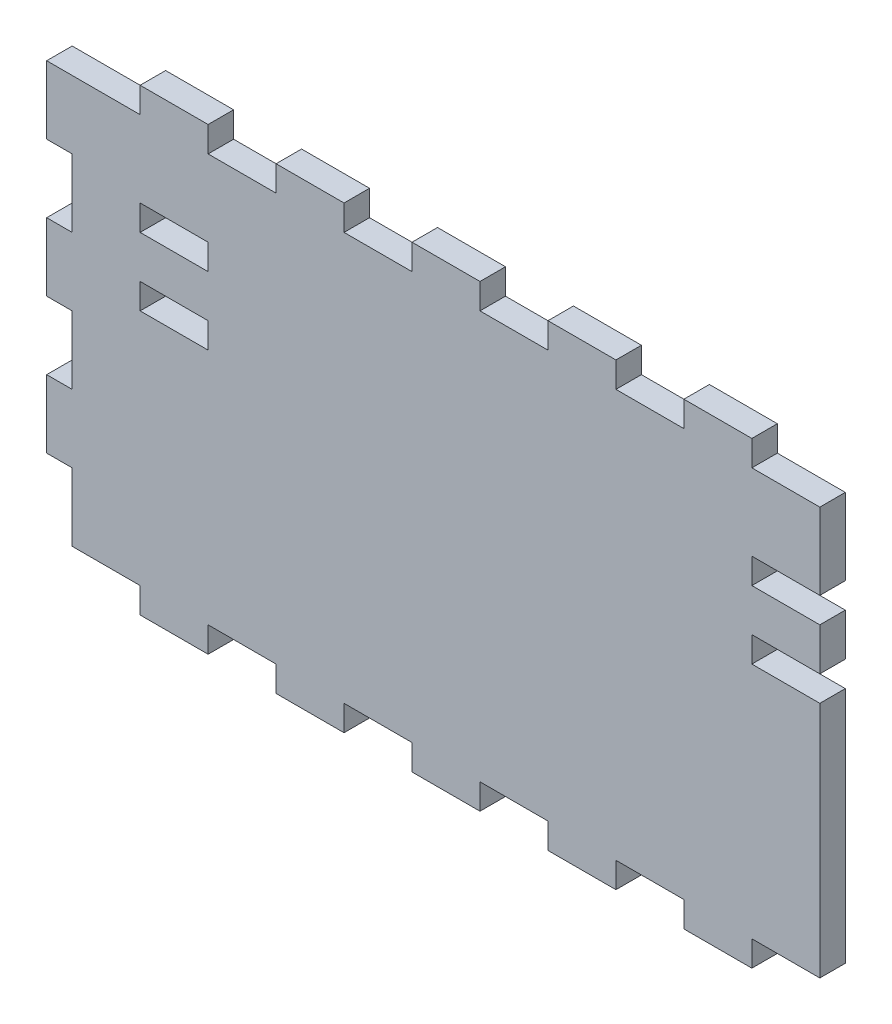
SolidWorks part; units mm, degrees
ref_plane "Front Plane" through (0, 0, 0) normal (0, 0, 1) x (1, 0, 0)
ref_plane "Top Plane" through (0, 0, 0) normal (0, 1, 0) x (1, 0, 0)
ref_plane "Right Plane" through (0, 0, 0) normal (1, 0, 0) x (0, 0, -1)
sketch "Sketch1" plane through (0, 0, 0) normal (0, 0, 1) x (1, 0, 0)
  line L1 (-139.7, -76.2) -> (139.7, -76.2)
  line L2 (-139.7, -76.2) -> (-139.7, 76.2)
  line L3 (-139.7, 76.2) -> (139.7, 76.2)
  line L4 (139.7, -76.2) -> (139.7, 76.2)
  line L5 (-139.7, -76.2) -> (139.7, 76.2) construction
  line L6 (-139.7, 76.2) -> (139.7, -76.2) construction
  point P0 (0, 0)
  dimension "D1" = 279.4
  dimension "D2" = 152.4
extrude "Boss-Extrude1" add sketch "Sketch1" along normal blind 9.525
sketch "Sketch2" plane through (0, -76.2, 0) normal (0, -1, 0) x (1, 0, 0)
  line L0 (-139.7, 0) -> (139.7, 0) construction
  line L1 (-114.3, 0) -> (-88.9, 0)
  line L2 (-114.3, 0) -> (-114.3, 9.525)
  line L3 (-114.3, 9.525) -> (-88.9, 9.525)
  line L4 (-88.9, 0) -> (-88.9, 9.525)
  line L5 (-139.7, 9.525) -> (139.7, 9.525) construction
  line L6 (-139.7, 9.525) -> (-139.7, 0) construction
  point P10 (-139.7, 4.7625)
  dimension "D1" = 25.4
  dimension "D2" = 25.4
extrude "Boss-Extrude2" add sketch "Sketch2" along normal blind 9.525
pattern_linear "LPattern1" count 5 spacing 50.8 along (1, 0, 0) of "Boss-Extrude2"
mirror "Mirror1" about plane through (0, 0, 0) normal (0, 1, 0) of "LPattern1"
sketch "Sketch3" plane through (-139.7, 0, 0) normal (-1, 0, 0) x (0, 0, 1)
  line L0 (0, 76.2) -> (0, -76.2) construction
  line L1 (9.525, 76.2) -> (0, 76.2)
  line L2 (9.525, 76.2) -> (9.525, 50.8)
  line L3 (9.525, 50.8) -> (0, 50.8)
  line L4 (0, 76.2) -> (0, 50.8)
  dimension "D1" = 25.4
extrude "Boss-Extrude3" add sketch "Sketch3" along normal blind 9.525
pattern_linear "LPattern2" count 3 spacing 50.8 along (0, -1, 0) of "Boss-Extrude3"
sketch "Sketch4" plane through (0, 0, 0) normal (0, 0, -1) x (-1, 0, 0)
  line L1 (-139.7, 12.7) -> (-114.3, 12.7)
  line L2 (-139.7, 12.7) -> (-139.7, 22.225)
  line L3 (-139.7, 22.225) -> (-114.3, 22.225)
  line L4 (-114.3, 12.7) -> (-114.3, 22.225)
  line L5 (-114.3, -76.2) -> (-139.7, -76.2) construction
  line L6 (-139.7, -76.2) -> (-139.7, 76.2) construction
  dimension "D1" = 25.4
  dimension "D2" = 9.525
  dimension "D4" = 88.9
extrude "Cut-Extrude1" cut sketch "Sketch4" against normal through all
pattern_linear "LPattern3" count 2 spacing 228.6 along (-1, 0, 0) of "Cut-Extrude1"
sketch "Sketch5" plane through (0, 0, 9.525) normal (0, 0, 1) x (1, 0, 0)
  line L1 (-88.9, 47.625) -> (-114.3, 47.625)
  line L2 (-88.9, 47.625) -> (-88.9, 38.1)
  line L3 (-88.9, 38.1) -> (-114.3, 38.1)
  line L4 (-114.3, 47.625) -> (-114.3, 38.1)
  line L5 (-88.9, -76.2) -> (-63.5, -76.2) construction
  line L8 (-114.3, 12.7) -> (-114.3, 22.225) construction
  dimension "D1" = 25.4
  dimension "D2" = 9.525
  dimension "D3" = 114.3
extrude "Cut-Extrude2" cut sketch "Sketch5" against normal through all
pattern_linear "LPattern4" count 2 spacing 228.6 along (1, 0, 0) of "Cut-Extrude2"
